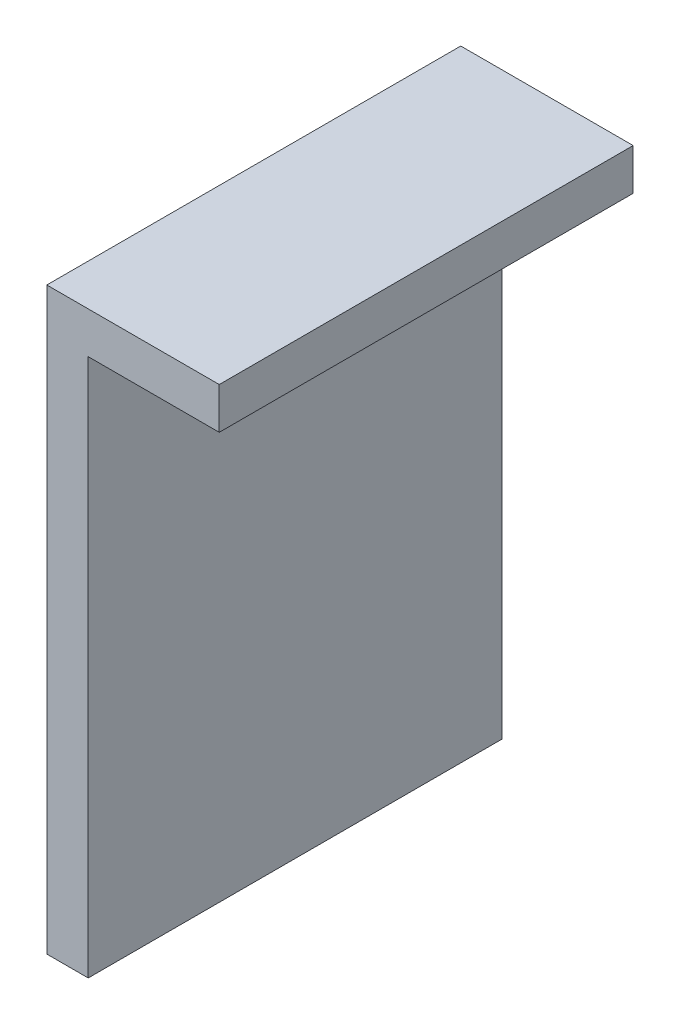
SolidWorks part; units mm, degrees
ref_plane "Front Plane" through (0, 0, 0) normal (0, 0, 1) x (1, 0, 0)
ref_plane "Top Plane" through (0, 0, 0) normal (0, 1, 0) x (1, 0, 0)
ref_plane "Right Plane" through (0, 0, 0) normal (1, 0, 0) x (0, 0, -1)
sketch "Sketch1" plane through (0, 0, 0) normal (0, 0, 1) x (1, 0, 0)
  line L0 (0, 0) -> (0, 42)
  line L1 (0, 42) -> (12.4964, 42)
  line L2 (12.4964, 42) -> (12.4964, 39)
  line L3 (12.4964, 39) -> (3, 39)
  line L4 (3, 39) -> (3, 0)
  line L5 (3, 0) -> (0, 0)
  dimension "D1" = 42
  dimension "D2" = 3
  dimension "D3" = 3
extrude "Boss-Extrude1" add sketch "Sketch1" along normal mid plane 30
